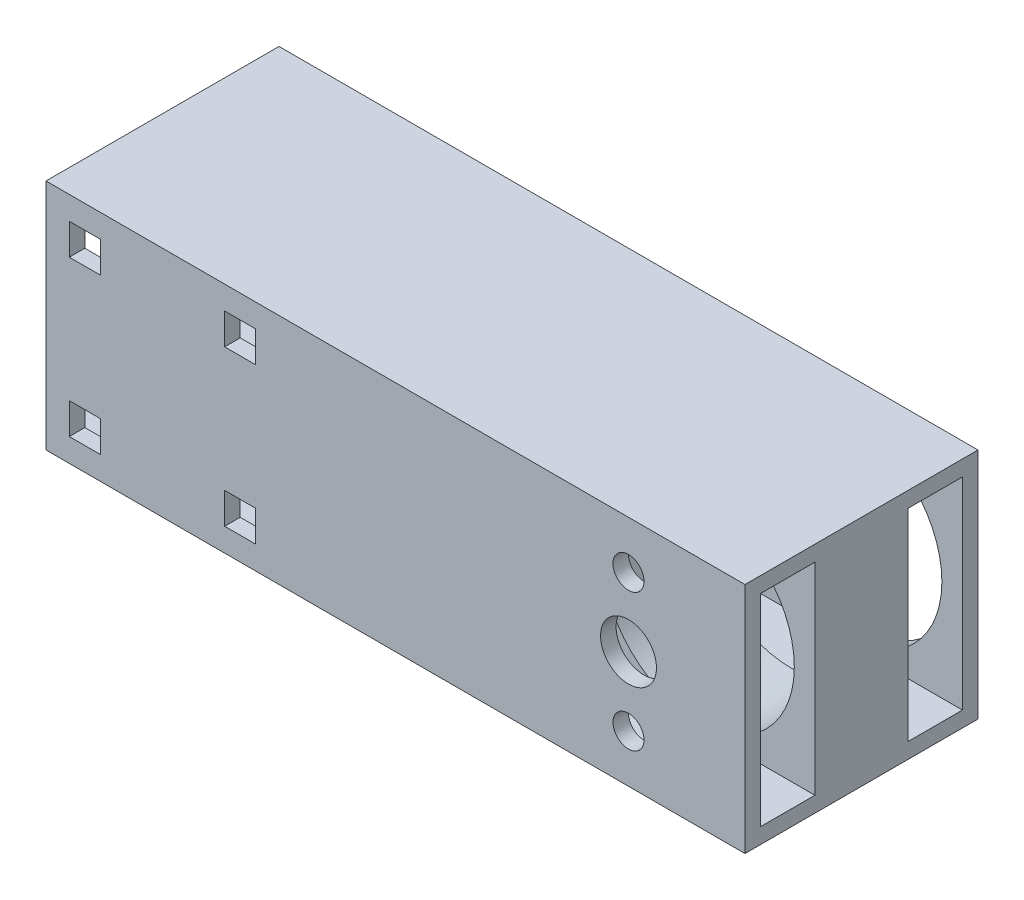
SolidWorks part; units mm, degrees
ref_plane "Front Plane" through (0, 0, 0) normal (0, 0, 1) x (1, 0, 0)
ref_plane "Top Plane" through (0, 0, 0) normal (0, 1, 0) x (1, 0, 0)
ref_plane "Right Plane" through (0, 0, 0) normal (1, 0, 0) x (0, 0, -1)
sketch "Sketch1" plane through (0, 0, 0) normal (1, 0, 0) x (0, 0, -1)
  line L1 (-15, -15) -> (15, -15)
  line L2 (-15, -15) -> (-15, 15)
  line L3 (-15, 15) -> (15, 15)
  line L4 (15, -15) -> (15, 15)
  line L5 (-15, -15) -> (15, 15) construction
  line L6 (-15, 15) -> (15, -15) construction
  line L11 (-5.1844, 5.1844) -> (5.1844, -5.1844) construction
  line L12 (-5.1844, -5.1844) -> (5.1844, 5.1844) construction
  line L13 (-13, 13) -> (-6, 13)
  line L14 (-13, 13) -> (-13, -13)
  line L15 (-13, -13) -> (-6, -13)
  line L16 (-6, 13) -> (-6, -13)
  line L17 (13, 13) -> (6, 13)
  line L18 (13, 13) -> (13, -13)
  line L19 (13, -13) -> (6, -13)
  line L20 (6, 13) -> (6, -13)
  point P0 (0, 0)
  point P7 (0, 0)
  dimension "D1" = 30
  dimension "D2" = 30
  dimension "D3" = 2
  dimension "D4" = 7
  dimension "D5" = 2
  dimension "D6" = 7
  dimension "D7" = 2
  dimension "D8" = 2
extrude "Boss-Extrude3" add sketch "Sketch1" along normal blind 90
sketch "Sketch6" plane through (0, 0, -15) normal (0, 0, -1) x (-1, 0, 0)
  line L0 (-90, -15) -> (-90, 15) construction
  circle A0 centre (-75, 0) radius 12.35
  dimension "D2" = 24.7
  dimension "D1" = 15
extrude "Cut-Extrude5" cut sketch "Sketch6" against normal blind 23
sketch "Sketch8" plane through (0, 0, 15) normal (0, 0, 1) x (1, 0, 0)
  line L0 (90, 15) -> (90, -15) construction
  circle A0 centre (75, 0) radius 3.6
  circle A1 centre (75, 8.85) radius 2
  circle A2 centre (75, -8.85) radius 2
  dimension "D2" = 7.2
  dimension "D5" = 4
  dimension "D6" = 4
  dimension "D1" = 15
  dimension "D3" = 8.85
  dimension "D4" = 8.85
extrude "Cut-Extrude6" cut sketch "Sketch8" against normal blind 17
sketch "Sketch9" plane through (0, 0, 0) normal (-1, 0, 0) x (0, 0, 1)
  line L0 (-6, 13) -> (6, 13)
  line L1 (-6, -13) -> (6, -13)
  line L2 (-6, 13) -> (-6, -13)
  line L3 (6, 13) -> (6, -13)
extrude "Cut-Extrude7" cut sketch "Sketch9" against normal blind 59
sketch "Sketch10" plane through (0, 0, -15) normal (0, 0, -1) x (-1, 0, 0)
  line L0 (0, 15) -> (-30, 15)
  line L1 (-90, 15) -> (0, 15) construction
  line L2 (-30, 15) -> (-30, -15)
  line L3 (-90, -15) -> (0, -15) construction
  line L4 (-30, -15) -> (0, -15)
  line L5 (-25, 10) -> (0, 10)
  line L6 (0, -15) -> (0, 15) construction
  line L7 (-25, 10) -> (-25, -15)
  line L9 (-3, 8) -> (-7, 8)
  line L10 (-3, 8) -> (-3, 12)
  line L11 (-3, 12) -> (-7, 12)
  line L12 (-7, 8) -> (-7, 12)
  line L13 (-3, 8) -> (-7, 12) construction
  line L14 (-3, 12) -> (-7, 8) construction
  line L15 (-27, 8) -> (-23, 8)
  line L16 (-27, 8) -> (-27, 12)
  line L17 (-27, 12) -> (-23, 12)
  line L18 (-23, 8) -> (-23, 12)
  line L19 (-27, 8) -> (-23, 12) construction
  line L20 (-27, 12) -> (-23, 8) construction
  line L22 (-27, -12) -> (-23, -12)
  line L23 (-27, -12) -> (-27, -8)
  line L24 (-27, -8) -> (-23, -8)
  line L25 (-23, -12) -> (-23, -8)
  line L26 (-27, -12) -> (-23, -8) construction
  line L27 (-27, -8) -> (-23, -12) construction
  line L28 (-3, -12) -> (-7, -12)
  line L29 (-3, -12) -> (-3, -8)
  line L30 (-3, -8) -> (-7, -8)
  line L31 (-7, -12) -> (-7, -8)
  line L32 (-3, -12) -> (-7, -8) construction
  line L33 (-3, -8) -> (-7, -12) construction
  circle A0 centre (-25, 10) radius 2
  circle A1 centre (-5, 10) radius 2
  circle A2 centre (-25, -10) radius 2
  circle A3 centre (-5, -10) radius 2
  point P30 (0, 0)
  point P31 (0, 0)
  point P40 (0, 0)
  point P41 (0, 0)
  point P42 (0, 0)
  point P43 (0, 0)
  dimension "D3" = 4
  dimension "D4" = 5
  dimension "D5" = 4
  dimension "D7" = 4
  dimension "D8" = 4
  dimension "D1" = 5
  dimension "D2" = 5
  dimension "D6" = 5
  dimension "D9" = 4
  dimension "D10" = 4
  dimension "D11" = 4
  dimension "D12" = 4
  dimension "D13" = 4
  dimension "D14" = 20
extrude "Cut-Extrude8" cut sketch "Sketch10" against normal blind 34 contours L17 L18 L15 L16 | L11 L12 L9 L10 | L24 L25 L22 L23 | L30 L31 L28 L29
